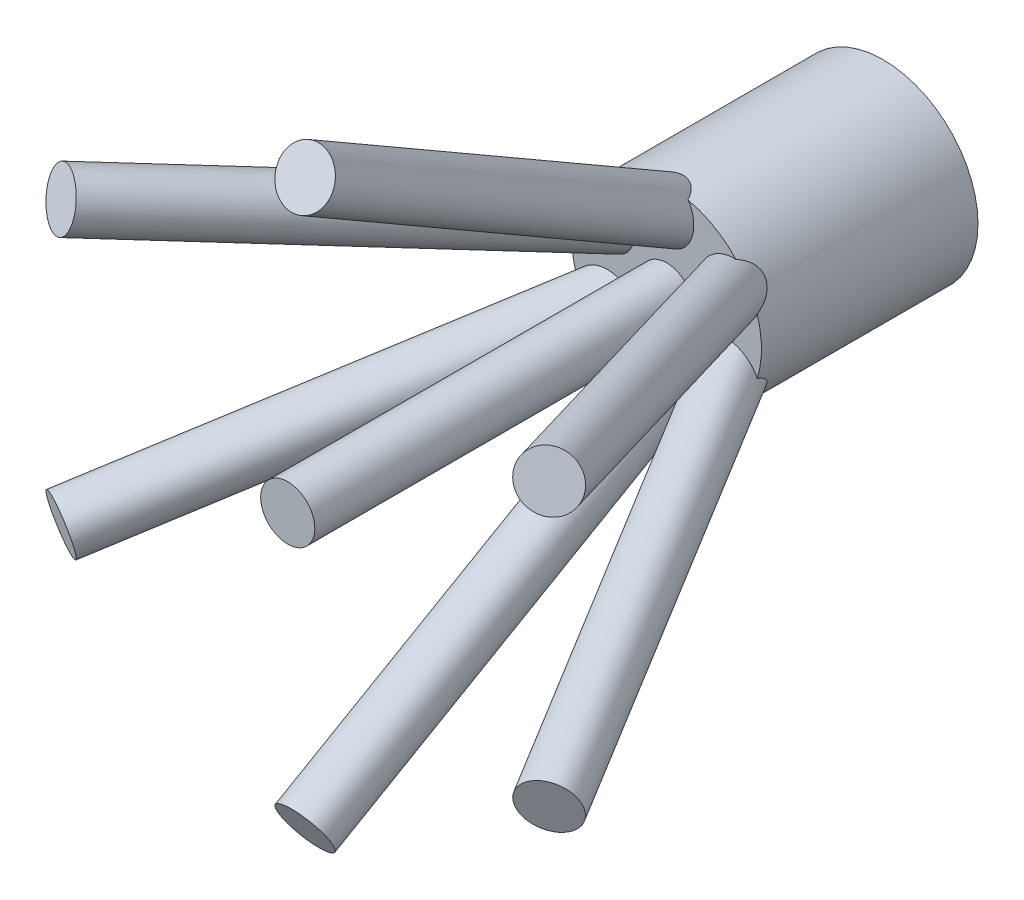
SolidWorks part; units mm, degrees
ref_plane "Front Plane" through (0, 0, 0) normal (0, 0, 1) x (1, 0, 0)
ref_plane "Top Plane" through (0, 0, 0) normal (0, 1, 0) x (1, 0, 0)
ref_plane "Right Plane" through (0, 0, 0) normal (1, 0, 0) x (0, 0, -1)
sketch "Sketch1" plane through (0, 0, 0) normal (0, 0, 1) x (1, 0, 0)
  circle A0 centre (0, 0) radius 0.4445
extrude "Extrude1" add sketch "Sketch1" along normal blind 1.016
sketch "Sketch2" plane through (0, 0, 1.016) normal (0, 0, 1) x (1, 0, 0)
  line L0 (0, 0.4445) -> (0, 0) construction
  circle A0 centre (0, 0) radius 0.127
  circle A2 centre (0, 0) radius 0.4445 construction
extrude "Extrude2" add sketch "Sketch2" along normal blind 1.778
ref_axis "Axis1" through (0, 0, 2.794) along (0, 0, -1)
sketch "Sketch5" plane through (0, 0, 0) normal (1, 0, 0) x (0, 0, -1)
  line L0 (-1.0163, 0.196) -> (-0.9528, 0.3059) construction
  line L1 (-0.8893, 0.4159) -> (-0.9528, 0.3059)
  line L2 (-1.0163, 0.196) -> (-0.9528, 0.196) construction
  line L3 (-2.649, 1.4319) -> (-0.8893, 0.4159)
  line L4 (-2.649, 1.4319) -> (-2.7125, 1.3219)
  line L5 (-2.7125, 1.3219) -> (-0.9528, 0.3059)
revolve "Revolve1" add sketch "Sketch5" angle 360 about L5
pattern_circular "CirPattern1" count 6 over 360 about axis through (0, 0, 2.794) along (0, 0, -1) of "Revolve1"
